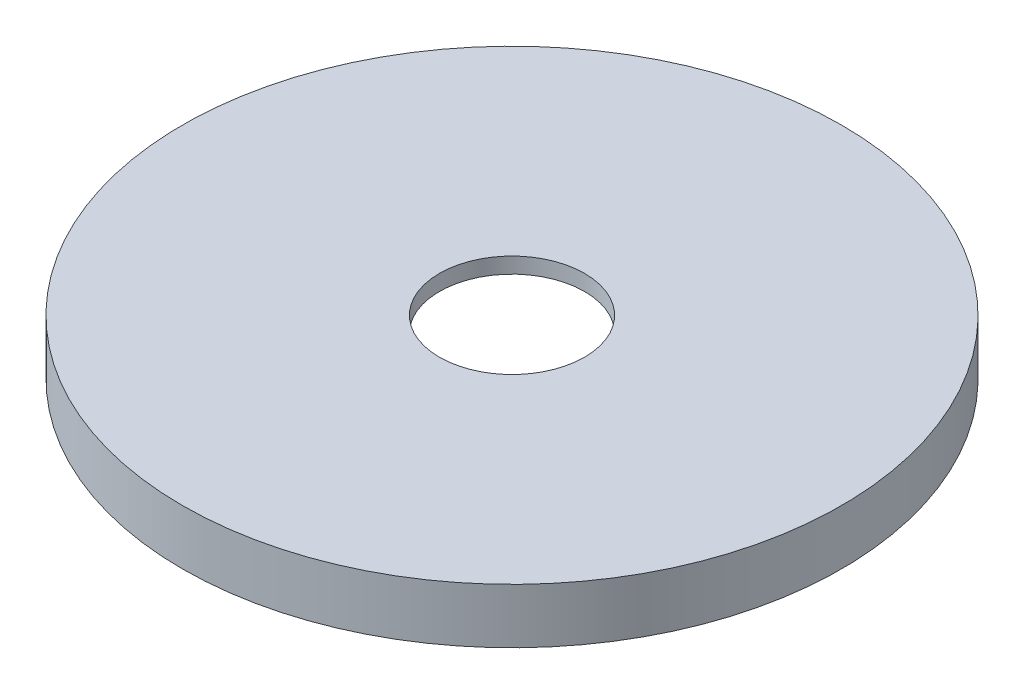
SolidWorks part; units mm, degrees
ref_plane "Alzado" through (0, 0, 0) normal (0, 0, 1) x (1, 0, 0)
ref_plane "Planta" through (0, 0, 0) normal (0, 1, 0) x (1, 0, 0)
ref_plane "Vista lateral" through (0, 0, 0) normal (1, 0, 0) x (0, 0, -1)
sketch "Croquis1" plane through (0, 0, 0) normal (0, 1, 0) x (1, 0, 0)
  circle A0 centre (0, 0) radius 84
  circle A1 centre (0, 0) radius 82
  dimension "D1" = 168
  dimension "D2" = 164
extrude "Saliente-Extruir1" add sketch "Croquis1" along normal blind 10
sketch "Croquis2" plane through (0, 10, 0) normal (0, 1, 0) x (1, 0, 0)
  circle A0 centre (0, 0) radius 84
  dimension "D1" = 168
extrude "Saliente-Extruir2" add sketch "Croquis2" along normal blind 4
sketch "Croquis3" plane through (0, 10, 0) normal (0, -1, 0) x (1, 0, 0)
  circle A0 centre (-20, 40) radius 1.5
  dimension "D1" = 3
  dimension "D6" = 40
  dimension "D7" = 20
extrude "Saliente-Extruir3" add sketch "Croquis3" along normal blind 10
ref_axis "Eje1" through (0, -0.7, 0) along (0, 1, 0)
pattern_circular "MatrizC1" count 4 every 90 about axis through (0, -0.7, 0) along (0, 1, 0) of "Saliente-Extruir3"
sketch "Croquis15" plane through (0, 0, 0) normal (0, -1, 0) x (1, 0, 0)
  circle A0 centre (0, 0) radius 82
  circle A1 centre (0, 0) radius 83
  dimension "D1" = 164
  dimension "D2" = 166
extrude "Cortar-Extruir1" cut sketch "Croquis15" against normal blind 5
sketch "Croquis16" plane through (0, 10, 0) normal (0, -1, 0) x (1, 0, 0)
  circle A0 centre (0, 0) radius 18.5
  dimension "D1" = 37
extrude "Cortar-Extruir2" cut sketch "Croquis16" against normal blind 13 contours A0
